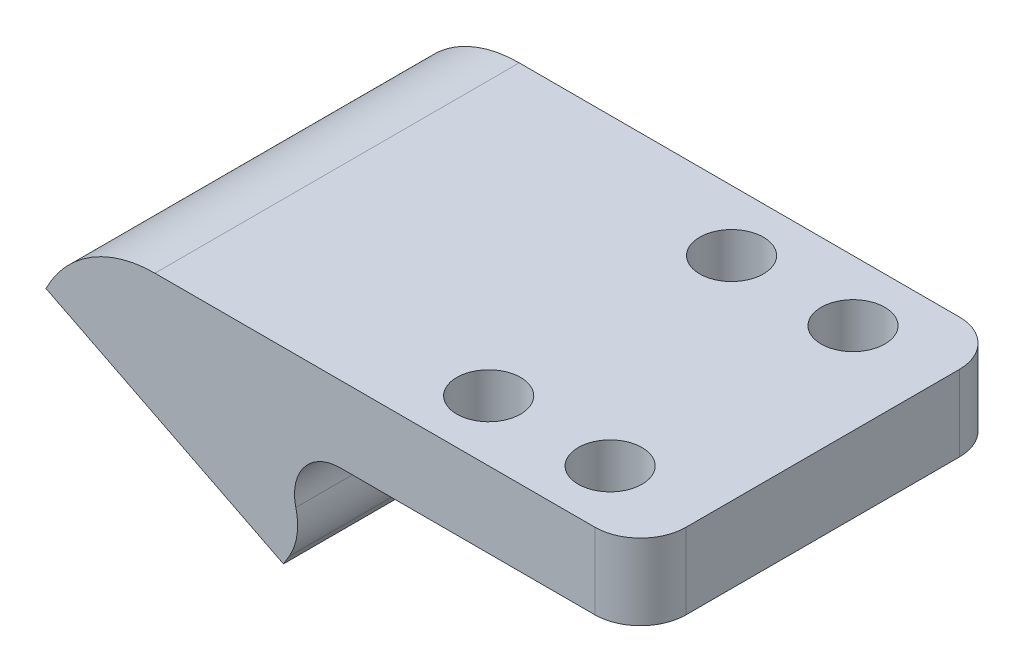
SolidWorks part; units mm, degrees
ref_plane "Plan de face" through (0, 0, 0) normal (0, 0, 1) x (1, 0, 0)
ref_plane "Plan de dessus" through (0, 0, 0) normal (0, 1, 0) x (1, 0, 0)
ref_plane "Plan de droite" through (0, 0, 0) normal (1, 0, 0) x (0, 0, -1)
sketch "Esquisse1" plane through (0, 0, 0) normal (0, 0, 1) x (1, 0, 0)
  line L1 (-6.5596, 0) -> (10.4404, 0)
  line L2 (-6.5596, 0) -> (-6.5596, 5)
  line L3 (-6.5596, 5) -> (10.4404, 5)
  line L4 (10.4404, 0) -> (10.4404, 5)
  dimension "D1" = 5
  dimension "D2" = 17
extrude "Boss.-Extru.1" add sketch "Esquisse1" along normal blind 24
sketch "Esquisse2" plane through (0, 0, 24) normal (0, 0, 1) x (1, 0, 0)
  line L0 (-6.5596, 5) -> (-16.4711, 5)
  line L1 (-16.4711, 5) -> (-0.5016, -3.0561)
  line L2 (-16.4711, 5) -> (-18.7231, 0.5359)
  line L3 (-18.7231, 0.5359) -> (-3.0805, -7.3553)
  line L4 (-3.0805, -7.3553) -> (-0.5016, -3.0561)
  line L5 (-6.5596, 5) -> (-6.5596, 0) construction
  line M4 (-6.5596, 5) -> (-6.5596, 0)
extrude "Boss.-Extru.2" add sketch "Esquisse2" against normal blind 24 contours L3 L4 L1 L2 | L0 L1 M4 region at (-9.8634, 3.3333, 24) region at (-9.6899, -1.2113, 24)
fillet "Congé1" radius 4 1 edges at (-0.5016, -3.0561, 12)
fillet "Congé2" radius 8 1 edges at (-16.4711, 5, 12)
fillet "Congé3" radius 3 1 edges at (-6.5596, 0, 12)
sketch "Esquisse3" plane through (10.4404, 0, 0) normal (1, 0, 0) x (0, 0, -1)
  line L1 (0, 0) -> (-24, 0)
  line L2 (0, 0) -> (0, 5)
  line L3 (0, 5) -> (-24, 5)
  line L4 (-24, 0) -> (-24, 5)
extrude "Boss.-Extru.3" add sketch "Esquisse3" along normal blind 10
sketch "Esquisse4" plane through (0, 5, 0) normal (0, 1, 0) x (1, 0, 0)
  line L0 (14.4404, -4) -> (6.4404, -4) construction
  line L2 (6.4404, -4) -> (6.4404, -20) construction
  line L3 (6.4404, -12) -> (20.4404, -12) construction
  line L4 (20.4404, 0) -> (20.4404, -24) construction
  circle A0 centre (6.4404, -4) radius 2.1
  circle A1 centre (14.4404, -4) radius 2.1
  circle A2 centre (6.4404, -20) radius 2.1
  circle A3 centre (14.4404, -20) radius 2.1
  circle A4 centre (6.4404, -20) radius 2.1
  dimension "D4" = 4.2
  dimension "D1" = 8
  dimension "D2" = 16
  dimension "D3" = 6
extrude "Enlèv. mat.-Extru.1" cut sketch "Esquisse4" against normal blind 10 contours A2 | A3 | A1 | A0 region at (6.4404, 5, 4) region at (14.4404, 5, 4) region at (6.4404, 5, 20) region at (14.4404, 5, 20)
fillet "Congé4" radius 3 2 edges at (20.4404, 2.5, 0) (20.4404, 2.5, 24)
sketch "Esquisse5" plane through (-3.5827, -7.102, 0) normal (-0.4504, -0.8928, 0) x (0.8928, -0.4504, 0)
  line L0 (-16.9578, 12) -> (0.5625, 12) construction
  line L1 (-16.9578, 0) -> (-16.9578, 24) construction
  line L2 (0.5625, 0) -> (0.5625, 24) construction
  line L4 (-16.9578, 0) -> (0.5625, 0) construction
  line L5 (-8.1977, 0) -> (-8.1977, 24) construction
  line L6 (-16.9578, 24) -> (0.5625, 24) construction
  circle A0 centre (-11.721, 15.4774) radius 2.482
  circle A1 centre (-5.1612, 15.4774) radius 0.4668
  circle A2 centre (-12.2677, 6.7) radius 3.4804
  circle A3 centre (-5.1612, 6.1677) radius 2.2402
